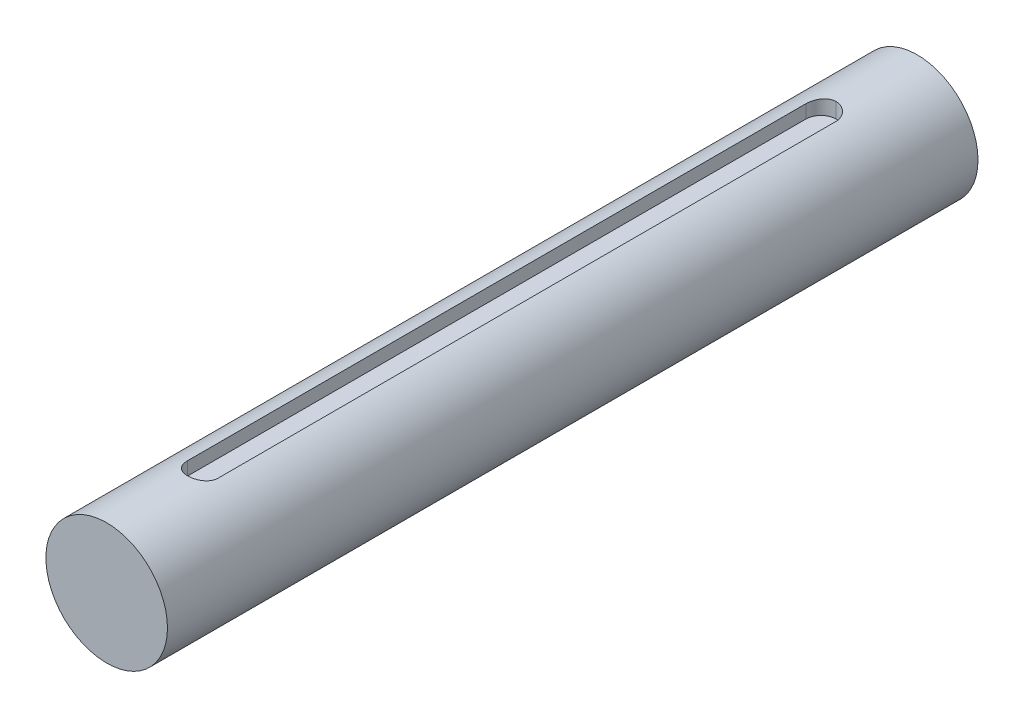
SolidWorks part; units mm, degrees
material "Alloy Steel"
ref_plane "Front Plane" through (0, 0, 0) normal (0, 0, 1) x (1, 0, 0)
ref_plane "Top Plane" through (0, 0, 0) normal (0, 1, 0) x (1, 0, 0)
ref_plane "Right Plane" through (0, 0, 0) normal (1, 0, 0) x (0, 0, -1)
sketch "Sketch1" plane through (0, 0, 0) normal (0, 0, 1) x (1, 0, 0)
  circle A0 centre (0, 0) radius 9.525
  dimension "D1" = 19.05
extrude "Extrude1" add sketch "Sketch1" along normal blind 127
sketch "Sketch2" plane through (0, 0, 127) normal (0, 0, 1) x (1, 0, 0)
  line L1 (2.3813, 7.1437) -> (-2.3813, 7.1437)
  line L2 (2.3813, 7.1437) -> (2.3813, 11.9062)
  line L3 (2.3813, 11.9062) -> (-2.3813, 11.9062)
  line L4 (-2.3813, 7.1437) -> (-2.3813, 11.9062)
  point P4 (0, 11.9062)
  dimension "D1" = 4.7625
  dimension "D2" = 4.7625
  dimension "D3" = 7.1437
extrude "Cut-Extrude1" cut sketch "Sketch2" against normal offset from surface (114.3 mm away) 12.7 up to face at (9.525, 0, 0)
sketch "Sketch4" plane through (0, 0, 127) normal (0, 0, 1) x (1, 0, 0)
  line L0 (-2.3813, 7.1437) -> (-2.3813, 9.2225) construction
  line L1 (2.3813, 7.1437) -> (-2.3813, 7.1437)
  line L2 (2.3813, 7.1437) -> (2.3813, 9.2225)
  line L4 (-2.3813, 7.1437) -> (-2.3813, 9.2225)
  arc A1 (-2.3813, 9.2225) -> (2.3813, 9.2225) centre (0, 0) ccw construction
  arc A2 (2.3813, 9.2225) -> (-2.3813, 9.2225) centre (0, 0) ccw
extrude "Extrude2" add sketch "Sketch4" against normal blind 12.7
fillet "Fillet1" radius 2.3813 4 edges at (2.3813, 8.1831, 114.3) (-2.3813, 8.1831, 114.3) (-2.3813, 8.1831, 12.7) (2.3813, 8.1831, 12.7)
